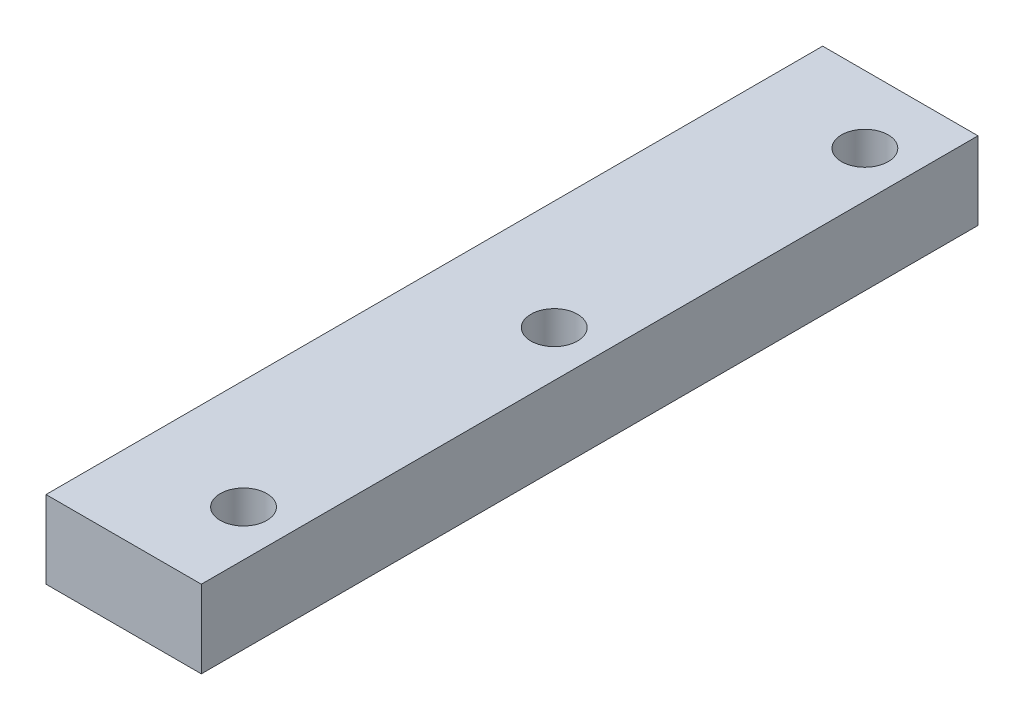
SolidWorks part; units mm, degrees
material "ABS"
ref_plane "Front Plane" through (0, 0, 0) normal (0, 0, 1) x (1, 0, 0)
ref_plane "Top Plane" through (0, 0, 0) normal (0, 1, 0) x (1, 0, 0)
ref_plane "Right Plane" through (0, 0, 0) normal (1, 0, 0) x (0, 0, -1)
sketch "Sketch1" plane through (0, 0, 0) normal (0, 0, 1) x (1, 0, 0)
  line L0 (20, 20.188) -> (0, 20.188)
  line L1 (0, 20.188) -> (0, 10.188)
  line L5 (20, 10.188) -> (20, 20.188)
  line L6 (0, 10.188) -> (20, 10.188)
  dimension "D1" = 20
  dimension "D2" = 10
  dimension "D3" = 10
extrude "Boss-Extrude1" add sketch "Sketch1" along normal blind 100
sketch "Sketch2" plane through (0, 20.188, 0) normal (0, 1, 0) x (1, 0, 0)
  circle A0 centre (14.1086, -8.6737) radius 3
extrude "Cut-Extrude1" cut sketch "Sketch2" against normal blind 140
pattern_linear "LPattern1" count 4 spacing 40 along (0, 0, 1) of "Cut-Extrude1"
